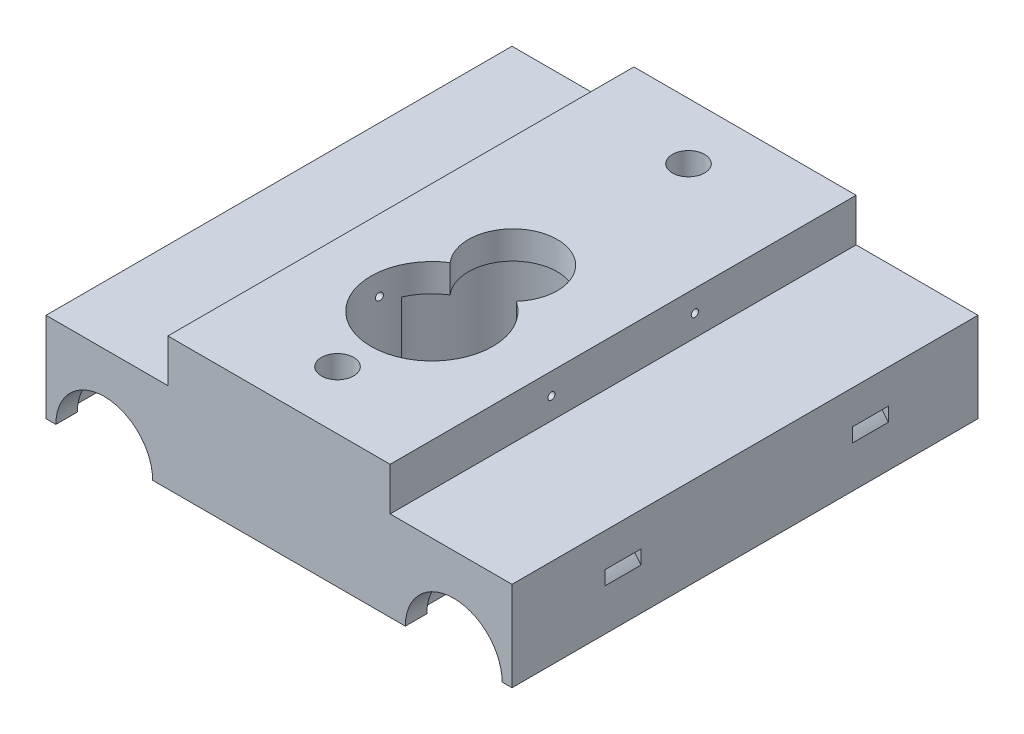
SolidWorks part; units mm, degrees
ref_plane "Спереди" through (0, 0, 0) normal (0, 0, 1) x (1, 0, 0)
ref_plane "Сверху" through (0, 0, 0) normal (0, 1, 0) x (1, 0, 0)
ref_plane "Справа" through (0, 0, 0) normal (1, 0, 0) x (0, 0, -1)
sketch "Эскиз1" plane through (0, 0, 0) normal (0, 1, 0) x (1, 0, 0)
  line L1 (-24.8662, 24.0482) -> (40.1338, 24.0482)
  line L2 (-24.8662, 24.0482) -> (-24.8662, -40.9518)
  line L3 (-24.8662, -40.9518) -> (40.1338, -40.9518)
  line L4 (40.1338, 24.0482) -> (40.1338, -40.9518)
  dimension "D1" = 65
extrude "Бобышка-Вытянуть1" add sketch "Эскиз1" along normal blind 17
ref_plane "Плоскость1" through (0, 0, 37.9518) normal (0, 0, 1) x (1, 0, 0)
sketch "Эскиз3" plane through (0, 0, 37.9518) normal (0, 0, 1) x (1, 0, 0)
  line L0 (7.6338, 20.5799) -> (-16.7362, 20.5799) construction
  line L1 (7.6338, 20.5799) -> (32.0038, 20.5799) construction
  line L2 (39.7538, 8.5) -> (40.1338, 8.5)
  line L3 (40.1338, 17) -> (40.1338, 0) construction
  line L4 (40.1338, 8.5) -> (40.1338, 0)
  line L5 (40.1338, 0) -> (24.2538, 0)
  line L6 (-24.8662, 0) -> (40.1338, 0) construction
  line L7 (24.2538, 0) -> (24.2538, 8.5)
  line L8 (-24.4862, 8.5) -> (-24.8662, 8.5)
  line L9 (-24.8662, 17) -> (-24.8662, 0) construction
  line L10 (-24.8662, 8.5) -> (-24.8662, 0)
  line L11 (-24.8662, 0) -> (-8.9862, 0)
  line L12 (-8.9862, 0) -> (-8.9862, 8.5)
  arc A0 (-8.9862, 8.5) -> (-24.4862, 8.5) centre (-16.7362, 8.5) ccw
  arc A1 (39.7538, 8.5) -> (24.2538, 8.5) centre (32.0038, 8.5) ccw
  dimension "D3" = 15.5
  dimension "D4" = 15.5
  dimension "D1" = 24.37
  dimension "D2" = 24.37
extrude "Вырез-Вытянуть1" cut sketch "Эскиз3" against normal blind 59
ref_plane "Плоскость3" through (0, 0, 13.4518) normal (0, 0, 1) x (1, 0, 0)
sketch "Эскиз5" plane through (0, 0, 40.9518) normal (0, 0, 1) x (1, 0, 0)
  line L0 (7.6338, 22.8915) -> (-16.7362, 22.8915) construction
  line L1 (7.6338, 22.8915) -> (32.0038, 22.8915) construction
  line L2 (-23.4862, 8.5) -> (-24.8662, 8.5)
  line L3 (-24.8662, 17) -> (-24.8662, 0) construction
  line L4 (-24.8662, 8.5) -> (-24.8662, 0)
  line L5 (-24.8662, 0) -> (-9.9862, 0)
  line L6 (-24.8662, 0) -> (40.1338, 0) construction
  line L7 (-9.9862, 0) -> (-9.9862, 8.5)
  line L8 (38.7538, 8.5) -> (40.1338, 8.5)
  line L9 (40.1338, 17) -> (40.1338, 0) construction
  line L10 (40.1338, 8.5) -> (40.1338, 0)
  line L11 (40.1338, 0) -> (25.2538, 0)
  line L12 (25.2538, 0) -> (25.2538, 8.5)
  arc A0 (-9.9862, 8.5) -> (-23.4862, 8.5) centre (-16.7362, 8.5) ccw
  arc A1 (38.7538, 8.5) -> (25.2538, 8.5) centre (32.0038, 8.5) ccw
  dimension "D3" = 13.5
  dimension "D4" = 13.5
  dimension "D1" = 24.37
  dimension "D2" = 24.37
extrude "Вырез-Вытянуть2" cut sketch "Эскиз5" against normal through all
sketch "Эскиз6" plane through (0, 0, 13.4518) normal (0, 0, 1) x (1, 0, 0)
  line L0 (-23.4862, 8.5) -> (-24.8662, 8.5)
  line L1 (-24.8662, 8.5) -> (-24.8662, 17)
  line L2 (-24.8662, 17) -> (-9.9862, 17)
  line L3 (-24.8662, 17) -> (40.1338, 17) construction
  line L4 (40.1338, 17) -> (40.1338, 8.5)
  line L5 (40.1338, 17) -> (40.1338, 8.5) construction
  line L6 (40.1338, 8.5) -> (38.7538, 8.5)
  line L7 (-9.9862, 8.5) -> (-9.9862, 0)
  line L8 (-9.9862, 0) -> (25.2538, 0)
  line L9 (25.2538, 0) -> (25.2538, 8.5)
  line L10 (-9.9862, 17) -> (40.1338, 17)
  arc A0 (-9.9862, 8.5) -> (-23.4862, 8.5) centre (-16.7362, 8.5) ccw
  arc A1 (38.7538, 8.5) -> (25.2538, 8.5) centre (32.0038, 8.5) ccw
extrude "Бобышка-Вытянуть2" add sketch "Эскиз6" against normal blind 10 contours L7 L8 L9 A1 L6 L4 L10 L2 L1 L0 A0
sketch "Эскиз12" plane through (0, 0, 40.9518) normal (0, 0, 1) x (1, 0, 0)
  line L0 (-9.9862, 8.5) -> (-9.9862, 0)
  line L1 (-9.9862, 0) -> (25.2538, 0)
  line L3 (25.2538, 0) -> (25.2538, 8.5)
  line L5 (25.2538, 8.5) -> (-9.9862, 8.5)
extrude "Вырез-Вытянуть5" cut sketch "Эскиз12" against normal through all
sketch "Эскиз17" plane through (0, 17, 0) normal (0, 1, 0) x (1, 0, 0)
  line L0 (-29.2175, -8.3313) -> (-29.2175, 16.1687) construction
  line L1 (-29.2175, -8.3313) -> (-29.2175, -32.8313) construction
  line L2 (7.6338, 34.0476) -> (7.6338, -69.5456) construction
  circle A0 centre (7.6338, 16.1687) radius 2.25
  circle A1 centre (7.6762, -32.8313) radius 2.25
  dimension "D3" = 4.5
  dimension "D4" = 4.5
  dimension "D1" = 24.5
  dimension "D2" = 24.5
extrude "Вырез-Вытянуть8" cut sketch "Эскиз17" against normal through all
sketch "Эскиз18" plane through (0, 17, 0) normal (0, 1, 0) x (1, 0, 0)
  line L1 (-24.8662, 24.0482) -> (40.1338, 24.0482)
  line L2 (-24.8662, 24.0482) -> (-24.8662, -40.9518)
  line L3 (-24.8662, -40.9518) -> (40.1338, -40.9518)
  line L4 (40.1338, 24.0482) -> (40.1338, -40.9518)
  circle A2 centre (7.6338, 16.1687) radius 2.25
  circle A3 centre (7.6762, -32.8313) radius 2.25
extrude "Бобышка-Вытянуть3" add sketch "Эскиз18" along normal blind 10
sketch "Эскиз9" plane through (0, 0, 37.9518) normal (0, 0, 1) x (1, 0, 0)
  circle A0 centre (-16.7362, 8.5) radius 10
  circle A1 centre (-16.7362, 8.5) radius 11.25
  circle A2 centre (32.0038, 8.5) radius 11.25
  circle A3 centre (32.0038, 8.5) radius 10
  dimension "D1" = 20
  dimension "D2" = 22.5
  dimension "D3" = 22.5
  dimension "D4" = 20
extrude "Вырез-Вытянуть3" cut sketch "Эскиз9" against normal blind 5 from offset 10 offset against normal yes
sketch "Эскиз10" plane through (0, 0, 13.4518) normal (0, 0, 1) x (1, 0, 0)
  circle A0 centre (-16.7362, 8.5) radius 11.25
  circle A1 centre (32.0038, 8.5) radius 11.25
  circle A2 centre (-16.7362, 8.5) radius 10
  circle A3 centre (32.0038, 8.5) radius 10
  dimension "D1" = 22.5
  dimension "D2" = 22.5
  dimension "D3" = 20
  dimension "D4" = 20
extrude "Вырез-Вытянуть4" cut sketch "Эскиз10" against normal blind 5 from offset 20 offset against normal yes
sketch "Эскиз19" plane through (40.1338, 0, 0) normal (1, 0, 0) x (0, 0, -1)
  line L0 (24.0482, 27) -> (24.0482, 8.5) construction
  line L1 (-40.9518, 27) -> (24.0482, 27)
  line L2 (-40.9518, 27) -> (-40.9518, 21)
  line L3 (-40.9518, 21) -> (24.0482, 21)
  line L4 (24.0482, 27) -> (24.0482, 21)
  dimension "D1" = 6
extrude "Вырез-Вытянуть9" cut sketch "Эскиз19" against normal blind 17
sketch "Эскиз20" plane through (-24.8662, 0, 0) normal (-1, 0, 0) x (0, 0, 1)
  line L1 (-24.0482, 27) -> (40.9518, 27)
  line L2 (-24.0482, 27) -> (-24.0482, 21)
  line L3 (-24.0482, 21) -> (40.9518, 21)
  line L4 (40.9518, 27) -> (40.9518, 21)
  line L5 (40.9518, 27) -> (40.9518, 8.5) construction
  dimension "D1" = 6
  dimension "D2" = 65
extrude "Вырез-Вытянуть10" cut sketch "Эскиз20" against normal blind 17
sketch "Эскиз21" plane through (23.1338, 0, 0) normal (1, 0, 0) x (0, 0, -1)
  line L0 (-8.4518, 31.4091) -> (-18.4518, 31.4091) construction
  line L1 (-18.4518, 31.4091) -> (1.5482, 31.4091) construction
  circle A0 centre (-18.4518, 24) radius 0.5
  circle A1 centre (1.5482, 24) radius 0.5
  dimension "D3" = 1
  dimension "D4" = 1
  dimension "D1" = 10
  dimension "D2" = 20
extrude "Вырез-Вытянуть11" cut sketch "Эскиз21" against normal through all
sketch "Эскиз13" plane through (0, 27, 0) normal (0, -1, 0) x (1, 0, 0)
  arc A0 (2.9621, 12.4074) -> (12.2503, 12.4699) centre (7.6338, 8.3313) ccw
  arc A3 (12.2503, 12.4699) -> (2.9621, 12.4074) centre (7.5583, 19.5576) ccw
  dimension "D1" = 12.4
extrude "Вырез-Вытянуть12" cut sketch "Эскиз13" along normal blind 3.9 contours A0 A3
sketch "Эскиз24" plane through (0, 23.1, 0) normal (0, 1, 0) x (1, 0, 0)
  arc A1 (-0.1902, -16.0633) -> (15.3532, -16.1678) centre (7.5583, -19.5576) ccw
  arc A2 (15.3532, -16.1678) -> (-0.1902, -16.0633) centre (7.6338, -8.3313) ccw
  dimension "D2" = 22
extrude "Вырез-Вытянуть13" cut sketch "Эскиз24" against normal through all
